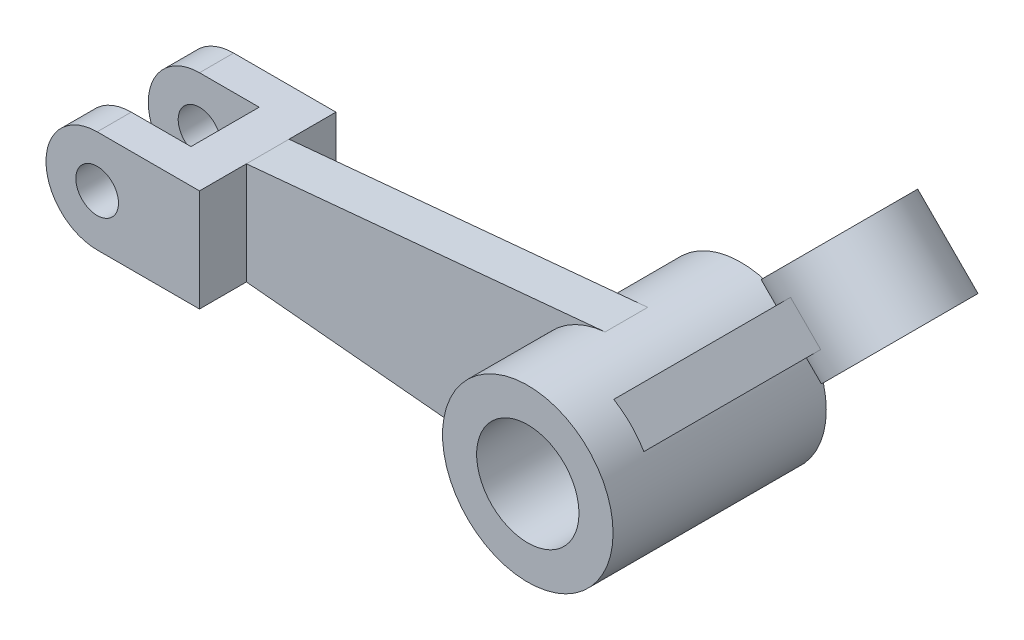
SolidWorks part; units mm, degrees
ref_plane "Front Plane" through (0, 0, 0) normal (0, 0, 1) x (1, 0, 0)
ref_plane "Top Plane" through (0, 0, 0) normal (0, 1, 0) x (1, 0, 0)
ref_plane "Right Plane" through (0, 0, 0) normal (1, 0, 0) x (0, 0, -1)
sketch "Sketch1" plane through (0, 0, 0) normal (0, 0, 1) x (1, 0, 0)
  line L0 (0, 0) -> (-10, 0) construction
  line L1 (0, 0) -> (26.0347, 26.0347) construction
  circle A0 centre (0, 0) radius 10
  circle A1 centre (0, 0) radius 6
  dimension "D1" = 20
  dimension "D2" = 12
  dimension "D3" = 45
extrude "Boss-Extrude1" add sketch "Sketch1" along normal mid plane 25
sketch "Sketch2" plane through (0, 0, 0) normal (0, 0, 1) x (1, 0, 0)
  line L0 (-55, 6) -> (-43, 6)
  line L1 (-43, 6) -> (-43, -6)
  line L2 (-43, -6) -> (-55, -6)
  line L3 (-43, 6) -> (-0.9364, 9.9561)
  line L4 (-43, -6) -> (-0.9364, -9.9561)
  arc A1 (-55, 6) -> (-55, -6) centre (-55, 0) ccw
  circle A2 centre (0, 0) radius 10 construction
  arc A3 (-0.9364, 9.9561) -> (-0.9364, -9.9561) centre (0, 0) ccw
  circle A4 centre (-55, 0) radius 2.5
  dimension "D1" = 12
  dimension "D2" = 55
  dimension "D4" = 5
  dimension "D3" = 18
extrude "Boss-Extrude2" add sketch "Sketch2" along normal mid plane 5 contours A3 L3 L1 L4 region at (-24.2494, 0, 0)
extrude "Boss-Extrude3" add sketch "Sketch2<3>" along normal mid plane 16 contours L0 A1 L2 L1 region at (-51.0202, 0, 0)
sketch "Sketch2<3>" plane through (0, 0, 0) normal (0, 0, 1) x (1, 0, 0) same geometry as "Sketch2"
sketch "Sketch3" plane through (0, 6, 0) normal (0, 1, 0) x (1, 0, 0)
  line L0 (-61, 8) -> (-61, -8) construction
  line L1 (-48, 4) -> (-61, 4)
  line L2 (-48, 4) -> (-48, -4)
  line L3 (-48, -4) -> (-61, -4)
  line L4 (-61, 4) -> (-61, -4)
  line L5 (-48, 4) -> (-61, -4) construction
  line L6 (-48, -4) -> (-61, 4) construction
  point P0 (-54.5, 0)
  dimension "D1" = 8
  dimension "D2" = 13
extrude "Cut-Extrude1" cut sketch "Sketch3" against normal through all
ref_plane "Plane1" through (0, 0, 0) normal (-0.7071, 0.7071, 0) x (0.7071, 0.7071, 0)
sketch "Sketch4" plane through (0, 0, 0) normal (-0.7071, 0.7071, 0) x (0.7071, 0.7071, 0)
  line L0 (8.9974, 7.5) -> (39, 7.5)
  line L2 (8.9974, 7.5) -> (8.9974, -7.5)
  line L3 (39, -7.5) -> (8.9974, -7.5)
  circle A1 centre (39, 0) radius 7.5
  circle A2 centre (39, 0) radius 4
  dimension "D3" = 15
  dimension "D4" = 8
  dimension "D1" = 39
  dimension "D2" = 15
extrude "Boss-Extrude4" add sketch "Sketch4" along normal mid plane 5 contours A1 L0 L2 L3 region at (14.9281, 14.9281, 0)
extrude "Boss-Extrude5" add sketch "Sketch4<5>" along normal mid plane 10 contours A1 A2 region at (31.2211, 31.2211, -5.1533)
sketch "Sketch4<5>" plane through (0, 0, 0) normal (-0.7071, 0.7071, 0) x (0.7071, 0.7071, 0) same geometry as "Sketch4"
fillet "Fillet1" [suppressed] radius 1
fillet "Fillet2" [suppressed] radius 1
fillet "Fillet3" [suppressed] radius 1
fillet "Fillet4" [suppressed] radius 1
